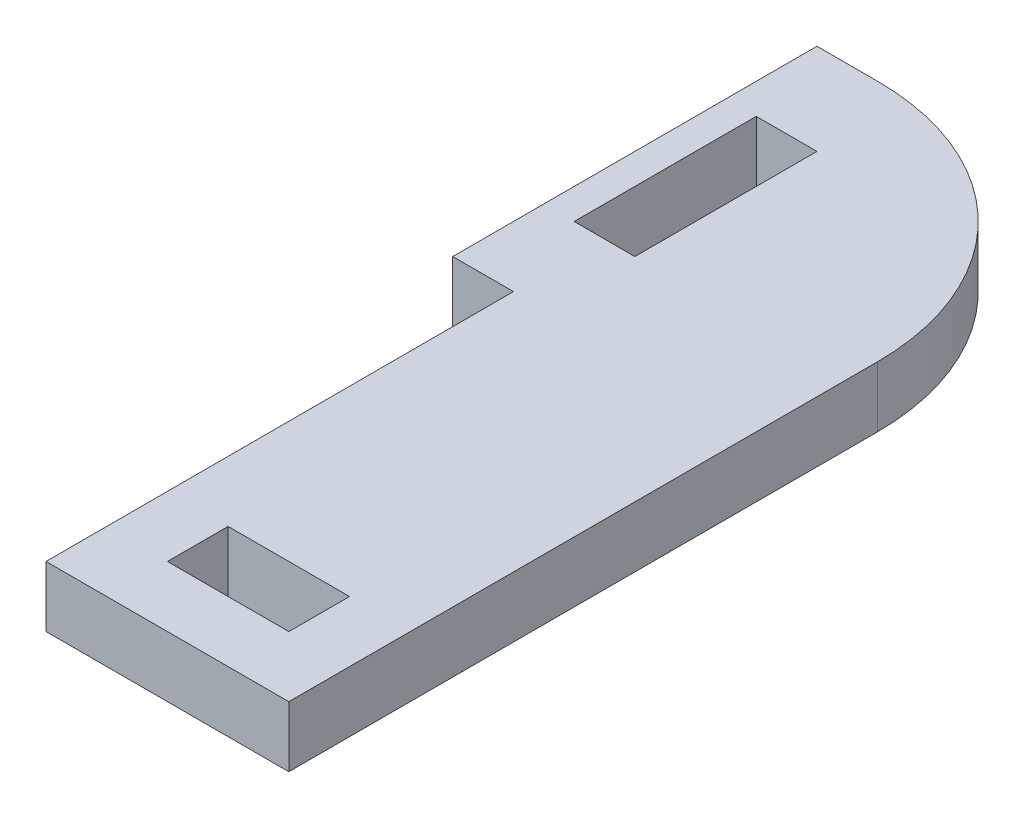
SolidWorks part; units mm, degrees
ref_plane "Front Plane" through (0, 0, 0) normal (0, 0, 1) x (1, 0, 0)
ref_plane "Top Plane" through (0, 0, 0) normal (0, 1, 0) x (1, 0, 0)
ref_plane "Right Plane" through (0, 0, 0) normal (1, 0, 0) x (0, 0, -1)
sketch "Sketch1" plane through (0, 0, 0) normal (0, 1, 0) x (1, 0, 0)
  line L9 (-20.0645, 77.5272) -> (-10.0645, 77.5272)
  line L10 (-20.0645, 77.5272) -> (-20.0645, 82.5272)
  line L11 (-20.0645, 82.5272) -> (-10.0645, 82.5272)
  line L12 (-10.0645, 77.5272) -> (-10.0645, 82.5272)
  line L14 (-30.0645, 111.0272) -> (-25.0645, 111.0272)
  line L15 (-30.0645, 111.0272) -> (-30.0645, 141.0272)
  line L19 (-25.0645, 72.5272) -> (-5.0645, 72.5272)
  line L24 (-27.5645, 118.5272) -> (-22.5645, 118.5272)
  line L25 (-27.5645, 118.5272) -> (-27.5645, 133.5272)
  line L26 (-27.5645, 133.5272) -> (-22.5645, 133.5272)
  line L27 (-22.5645, 118.5272) -> (-22.5645, 133.5272)
  line L29 (-5.0645, 141.0272) -> (-5.0645, 72.5272)
  line L31 (-30.0645, 141.0272) -> (-5.0645, 141.0272)
  line L32 (-25.0645, 72.5272) -> (-25.0645, 111.0272)
  point P14 (-27.5645, 120.0272)
  dimension "D2" = 5
  dimension "D5" = 5
  dimension "D7" = 5
  dimension "D10" = 30
  dimension "D14" = 15
  dimension "D15" = 2.5
  dimension "D17" = 36
  dimension "D18" = 7.5
extrude "Boss-Extrude1" add sketch "Sketch1" along normal blind 5
fillet "Fillet2" radius 20 1 edges at (-5.0645, 2.5, -141.0272)
